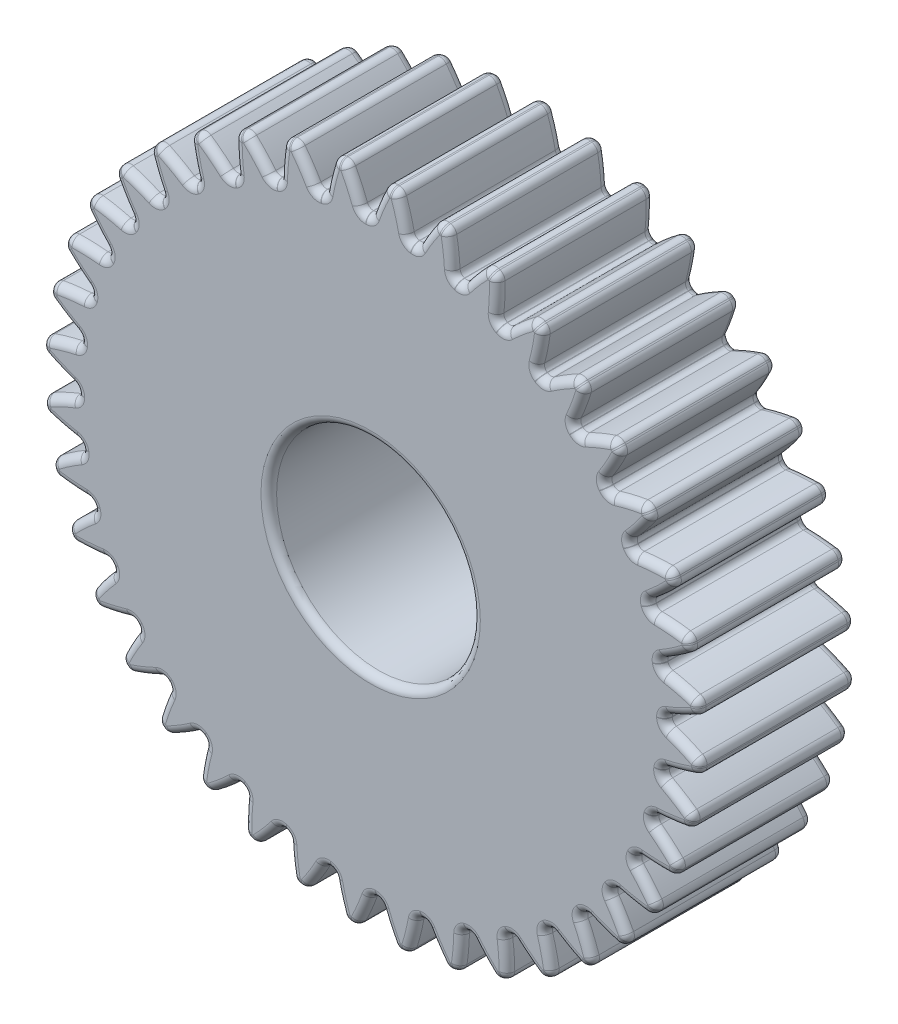
SolidWorks part; units mm, degrees
ref_plane "Front Plane" through (0, 0, 0) normal (1, 0, 0) x (0, 1, 0)
ref_plane "Top Plane" through (0, 0, 0) normal (0, 0, 1) x (0, 1, 0)
ref_plane "Right Plane" through (0, 0, 0) normal (0, 1, 0) x (-1, 0, 0)
sketch "Sketch1" plane through (0, 0, 0) normal (0, 0, 1) x (0, 1, 0)
  line L1 (0, 0) -> (0, 18.7939) construction
  line L2 (0, 0) -> (7.1921, 17.3633) construction
  line L3 (0, 0) -> (13.2893, 13.2893) construction
  line L4 (0, 0) -> (17.3633, 7.1921) construction
  line L5 (0, 0) -> (18.7939, 0) construction
  line L6 (7.1921, 17.3633) -> (0.3736, 20.1876) construction
  line L8 (13.2893, 13.2893) -> (2.8519, 23.7266) construction
  line L9 (17.3633, 7.1921) -> (8.8903, 27.6477) construction
  line L11 (18.7939, 0) -> (18.7939, 29.5213) construction
  line L12 (0, 0) -> (1.2411, 19.9615) construction
  line L14 (2.328, 18.6491) -> (0, 0) construction
  line L17 (0, 18.7939) -> (0, 18.75)
  line L18 (2.328, 18.6491) -> (2.3226, 18.6056)
  line L19 (0.4565, 19.9948) -> (0, 0) construction
  circle A16 centre (0, 0) radius 18.7939 construction
  arc A17 (1.6748, 20.9331) -> (0.9311, 20.9793) centre (0, 0) ccw
  circle A18 centre (0, 0) radius 18.75
  arc A19 (0, 20) -> (2.4774, 19.846) centre (0, 0) ccw construction
  arc A20 (0, 20) -> (2.4774, 19.846) centre (0, 0) cw
  arc A21 (0, 18.7939) -> (8.8903, 27.6477) centre (13.1457, 14.4844) cw construction
  arc A22 (2.328, 18.6491) -> (-5.397, 28.536) centre (-11.2502, 16.0012) ccw construction
  arc A23 (0, 18.7939) -> (0.9311, 20.9793) centre (13.1457, 14.4844) cw
  arc A24 (1.6748, 20.9331) -> (2.328, 18.6491) centre (-11.2502, 16.0012) cw
  circle A25 centre (0, 0) radius 6.5
  point P12 (0, 0)
  dimension "BaseCircle" = 37.5877
  dimension "AddendumCircle" = 42
  dimension "RootCircle" = 37.5
  dimension "PitchCircle" = 40
  dimension "D6" = 13
  dimension "D2" = 29.5213
  dimension "D3" = 22.141
  dimension "D4" = 14.7607
  dimension "D5" = 7.3803
  dimension "D7" = 2.25
  dimension "D1" = 5
sketch "Sketch2" plane through (0, 0, 0) normal (0, 0, 1) x (0, 1, 0)
  line L8 (2.328, 18.6491) -> (2.3226, 18.6056) construction
  line L9 (0, 18.7939) -> (0, 18.75) construction
  line L10 (2.328, 18.6491) -> (2.3226, 18.6056)
  line L11 (0, 18.7939) -> (0, 18.75)
  arc A0 (1.6748, 20.9331) -> (0.9311, 20.9793) centre (0, 0) ccw construction
  arc A1 (1.6748, 20.9331) -> (0.9311, 20.9793) centre (0, 0) ccw
  arc A7 (0.9311, 20.9793) -> (0, 18.7939) centre (13.1457, 14.4844) ccw construction
  arc A8 (0.9311, 20.9793) -> (0, 18.7939) centre (13.1457, 14.4844) ccw
  arc A9 (2.328, 18.6491) -> (1.6748, 20.9331) centre (-11.2502, 16.0012) ccw construction
  arc A10 (2.328, 18.6491) -> (1.6748, 20.9331) centre (-11.2502, 16.0012) ccw
  circle A12 centre (0, 0) radius 18.75 construction
  arc A13 (2.3226, 18.6056) -> (0, 18.75) centre (0, 0) ccw
extrude "Boss-Extrude5" add sketch "Sketch1" along normal blind 10 contours A18 A19 A20
extrude "Boss-Extrude6" add sketch "Sketch2" along normal blind 10
fillet "Fillet3" radius 0.5 4 edges at (-20.9331, 1.6748, 5) (-20.9793, 0.9311, 5) (-18.7939, 0, 5) (-18.6491, 2.328, 5)
fillet "Fillet4" radius 0.4 2 edges at (-18.75, 0, 5) (-18.6056, 2.3226, 5)
pattern_circular "CirPattern5" count 40 over 360 about axis through (0, 0, 0) along (0, 0, 1) of "Boss-Extrude6", "Fillet3", "Fillet4"
fillet "Fillet2" radius 0.5 1 edges at (6.5, 0, 10)
fillet "Fillet5" radius 0.5 641 edges at (-15.8347, 11.9994, 10) (-16.331, 13.0734, 10) (-15.922, 13.5686, 10) (-13.8991, 15.7421, 0) (-13.8991, 15.7421, 10) (-13.7626, 14.3287, 0) (-14.0848, 15.4672, 0) (-13.6033, 15.8923, 0) (-13.7626, 14.3287, 10) (-14.0848, 15.4672, 10) (-13.6033, 15.8923, 10) (-11.2654, 17.7226, 0) (-11.2654, 17.7226, 10) (-11.3517, 16.3052, 0) (-11.4918, 17.4801, 0) (-10.9498, 17.8246, 0) (-11.3517, 16.3052, 10) (-11.4918, 17.4801, 10) (-10.9498, 17.8246, 10) (-8.3543, 19.2667, 0) (-8.3543, 19.2667, 10) (-8.6612, 17.8803, 0) (-8.6158, 19.0626, 0) (-8.0266, 19.3181, 0) (-8.6612, 17.8803, 10) (-8.6158, 19.0626, 10) (-8.0266, 19.3181, 10) (-5.2375, 20.3364, 0) (-5.2375, 20.3364, 10) (-5.7575, 19.0151, 0) (-5.5277, 20.1757, 0) (-4.9057, 20.3359, 0) (-5.7575, 19.0151, 10) (-5.5277, 20.1757, 10) (-4.9057, 20.3359, 10) (-1.9917, 20.9053, 0) (-1.9917, 20.9053, 10) (-2.712, 19.6816, 0) (-2.3035, 20.792, 0) (-1.6641, 20.853, 0) (-2.712, 19.6816, 10) (-2.3035, 20.792, 10) (-1.6641, 20.853, 10) (1.3032, 20.9595, 0) (1.3032, 20.9595, 10) (0.4003, 19.8636, 0) (0.9775, 20.8964, 0) (1.6185, 20.8565, 0) (0.4003, 19.8636, 10) (0.9775, 20.8964, 10) (1.6185, 20.8565, 10) (4.5659, 20.4976, 0) (4.5659, 20.4976, 10) (3.5027, 19.5564, 0) (4.2344, 20.4862, 0) (4.8613, 20.3466, 0) (3.5027, 19.5564, 10) (4.2344, 20.4862, 10) (4.8613, 20.3466, 10) (7.7162, 19.531, 0) (7.7162, 19.531, 10) (6.5189, 18.7677, 0) (7.387, 19.5716, 0) (7.9843, 19.3356, 0) (6.5189, 18.7677, 10) (7.387, 19.5716, 10) (7.9843, 19.3356, 10) (10.6766, 18.0834, 0) (10.6766, 18.0834, 10) (9.3745, 17.5168, 0) (10.3577, 18.1751, 0) (10.9108, 17.8485, 0) (9.3745, 17.5168, 10) (10.3577, 18.1751, 10) (10.9108, 17.8485, 10) (13.374, 16.1906, 0) (13.374, 16.1906, 10) (11.9994, 15.8347, 0) (13.0734, 16.331, 0) (13.5686, 15.922, 0) (11.9994, 15.8347, 10) (13.0734, 16.331, 10) (13.5686, 15.922, 10) (15.7421, 13.8991, 0) (15.7421, 13.8991, 10) (14.3287, 13.7626, 0) (15.4672, 14.0848, 0) (15.8923, 13.6033, 0) (14.3287, 13.7626, 10) (15.4672, 14.0848, 10) (15.8923, 13.6033, 10) (17.7226, 11.2654, 0) (17.7226, 11.2654, 10) (16.3052, 11.3517, 0) (17.4801, 11.4918, 0) (17.8246, 10.9498, 0) (16.3052, 11.3517, 10) (17.4801, 11.4918, 10) (17.8246, 10.9498, 10) (19.2667, 8.3543, 0) (19.2667, 8.3543, 10) (17.8803, 8.6612, 0) (19.0626, 8.6158, 0) (19.3181, 8.0266, 0) (17.8803, 8.6612, 10) (19.0626, 8.6158, 10) (19.3181, 8.0266, 10) (20.3364, 5.2375, 0) (20.3364, 5.2375, 10) (19.0151, 5.7575, 0) (20.1757, 5.5277, 0) (20.3359, 4.9057, 0) (19.0151, 5.7575, 10) (20.1757, 5.5277, 10) (20.3359, 4.9057, 10) (20.9053, 1.9917, 0) (20.9053, 1.9917, 10) (19.6816, 2.712, 0) (20.792, 2.3035, 0) (20.853, 1.6641, 0) (19.6816, 2.712, 10) (20.792, 2.3035, 10) (20.853, 1.6641, 10) (20.9595, -1.3032, 0) (20.9595, -1.3032, 10) (19.8636, -0.4003, 0) (20.8964, -0.9775, 0) (20.8565, -1.6185, 0) (19.8636, -0.4003, 10) (20.8964, -0.9775, 10) (20.8565, -1.6185, 10) (20.4976, -4.5659, 0) (20.4976, -4.5659, 10) (19.5564, -3.5027, 0) (20.4862, -4.2344, 0) (20.3466, -4.8613, 0) (19.5564, -3.5027, 10) (20.4862, -4.2344, 10) (20.3466, -4.8613, 10) (19.531, -7.7162, 0) (19.531, -7.7162, 10) (18.7677, -6.5189, 0) (19.5716, -7.387, 0) (19.3356, -7.9843, 0) (18.7677, -6.5189, 10) (19.5716, -7.387, 10) (19.3356, -7.9843, 10) (18.0834, -10.6766, 0) (18.0834, -10.6766, 10) (17.5168, -9.3745, 0) (18.1751, -10.3577, 0) (17.8485, -10.9108, 0) (17.5168, -9.3745, 10) (18.1751, -10.3577, 10) (-20.9595, 1.3032, 0) (17.8485, -10.9108, 10) (16.1906, -13.374, 0) (16.1906, -13.374, 10) (15.8347, -11.9994, 0) (-20.9595, 1.3032, 10) (16.331, -13.0734, 0) (15.922, -13.5686, 0) (15.8347, -11.9994, 10) (16.331, -13.0734, 10) (15.922, -13.5686, 10) (13.8991, -15.7421, 0) (13.8991, -15.7421, 10) (13.7626, -14.3287, 0) (14.0848, -15.4672, 0) (13.6033, -15.8923, 0) (13.7626, -14.3287, 10) (14.0848, -15.4672, 10) (13.6033, -15.8923, 10) (11.2654, -17.7226, 0) (11.2654, -17.7226, 10) (11.3517, -16.3052, 0) (-19.8636, 0.4003, 0) (11.4918, -17.4801, 0) (10.9498, -17.8246, 0) (11.3517, -16.3052, 10) (11.4918, -17.4801, 10) (10.9498, -17.8246, 10) (8.3543, -19.2667, 0) (8.3543, -19.2667, 10) (8.6612, -17.8803, 0) (8.6158, -19.0626, 0) (8.0266, -19.3181, 0) (8.6612, -17.8803, 10) (8.6158, -19.0626, 10) (8.0266, -19.3181, 10) (5.2375, -20.3364, 0) (5.2375, -20.3364, 10) (5.7575, -19.0151, 0) (5.5277, -20.1757, 0) (4.9057, -20.3359, 0) (5.7575, -19.0151, 10) (5.5277, -20.1757, 10) (4.9057, -20.3359, 10) (-20.8964, 0.9775, 0) (1.9917, -20.9053, 0) (1.9917, -20.9053, 10) (2.712, -19.6816, 0) (2.3035, -20.792, 0) (1.6641, -20.853, 0) (2.712, -19.6816, 10) (2.3035, -20.792, 10) (1.6641, -20.853, 10) (-20.8565, 1.6185, 0) (-1.3032, -20.9595, 0) (-1.3032, -20.9595, 10) (-0.4003, -19.8636, 0) (-0.9775, -20.8964, 0) (-1.6185, -20.8565, 0) (-0.4003, -19.8636, 10) (-0.9775, -20.8964, 10) (-1.6185, -20.8565, 10) (-4.5659, -20.4976, 0) (-4.5659, -20.4976, 10) (-3.5027, -19.5564, 0) (-4.2344, -20.4862, 0) (-4.8613, -20.3466, 0) (-3.5027, -19.5564, 10) (-4.2344, -20.4862, 10) (-4.8613, -20.3466, 10) (-7.7162, -19.531, 0) (-7.7162, -19.531, 10) (-6.5189, -18.7677, 0) (-7.387, -19.5716, 0) (-7.9843, -19.3356, 0) (-6.5189, -18.7677, 10) (-7.387, -19.5716, 10) (-7.9843, -19.3356, 10) (-19.8636, 0.4003, 10) (-10.6766, -18.0834, 0) (-10.6766, -18.0834, 10) (-9.3745, -17.5168, 0) (-10.3577, -18.1751, 0) (-10.9108, -17.8485, 0) (-9.3745, -17.5168, 10) (-10.3577, -18.1751, 10) (-10.9108, -17.8485, 10) (-13.374, -16.1906, 0) (-13.374, -16.1906, 10) (-11.9994, -15.8347, 0) (-13.0734, -16.331, 0) (-13.5686, -15.922, 0) (-11.9994, -15.8347, 10) (-13.0734, -16.331, 10) (-13.5686, -15.922, 10) (-20.8964, 0.9775, 10) (-15.7421, -13.8991, 0) (-15.7421, -13.8991, 10) (-14.3287, -13.7626, 0) (-15.4672, -14.0848, 0) (-15.8923, -13.6033, 0) (-14.3287, -13.7626, 10) (-15.4672, -14.0848, 10) (-15.8923, -13.6033, 10) (-20.8565, 1.6185, 10) (-17.7226, -11.2654, 0) (-17.7226, -11.2654, 10) (-16.3052, -11.3517, 0) (-17.4801, -11.4918, 0) (-17.8246, -10.9498, 0) (-16.3052, -11.3517, 10) (-17.4801, -11.4918, 10) (-17.8246, -10.9498, 10) (-19.2667, -8.3543, 0) (-19.2667, -8.3543, 10) (-17.8803, -8.6612, 0) (-19.0626, -8.6158, 0) (-19.3181, -8.0266, 0) (-17.8803, -8.6612, 10) (-19.0626, -8.6158, 10) (-19.3181, -8.0266, 10) (-20.3364, -5.2375, 0) (-20.3364, -5.2375, 10) (-19.0151, -5.7575, 0) (-20.1757, -5.5277, 0) (-20.3359, -4.9057, 0) (-19.0151, -5.7575, 10) (-20.1757, -5.5277, 10) (-20.3359, -4.9057, 10) (-20.9053, -1.9917, 0) (-20.9053, -1.9917, 10) (-19.6816, -2.712, 0) (-20.792, -2.3035, 0) (-20.853, -1.6641, 0) (-19.6816, -2.712, 10) (-20.792, -2.3035, 10) (-20.853, -1.6641, 10) (-18.5649, 2.6282, 0) (-18.5649, 2.6282, 10) (-19.1941, 5.1291, 0) (-19.1941, 5.1291, 10) (-18.6025, 2.8772, 0) (6.5, 0, 0) (-18.6025, 2.8772, 10) (-18.0649, 5.2906, 0) (-18.0649, 5.2906, 10) (-17.9252, 5.5001, 0) (-17.9252, 5.5001, 10) (-18.1554, 8.0686, 0) (-18.1554, 8.0686, 10) (-17.9234, 5.7518, 0) (-17.9234, 5.7518, 10) (-17.0148, 8.0514, 0) (-17.0148, 8.0514, 10) (-16.8441, 8.2365, 0) (-16.8441, 8.2365, 10) (-16.6697, 10.8094, 0) (-16.6697, 10.8094, 10) (-16.8029, 8.4848, 0) (-16.8029, 8.4848, 10) (-15.5458, 10.614, 0) (-15.5458, 10.614, 10) (-15.3482, 10.7701, 0) (-15.3482, 10.7701, 10) (-14.7735, 13.284, 0) (-14.7735, 13.284, 10) (-15.2687, 11.0089, 0) (-15.2687, 11.0089, 10) (-13.694, 12.9153, 0) (-13.694, 12.9153, 10) (-13.4745, 13.0384, 0) (-13.4745, 13.0384, 10) (-12.5135, 15.4315, 0) (-12.5135, 15.4315, 10) (-13.3586, 13.262, 0) (-13.3586, 13.262, 10) (-11.5051, 14.8985, 0) (-11.5051, 14.8985, 10) (-11.2689, 14.9858, 0) (-11.2689, 14.9858, 10) (-9.9455, 17.1991, 0) (-9.9455, 17.1991, 10) (-11.1195, 15.1884, 0) (-11.1195, 15.1884, 10) (-9.0328, 16.5148, 0) (-9.0328, 16.5148, 10) (-8.7859, 16.5641, 0) (-8.7859, 16.5641, 10) (-7.1325, 18.5432, 0) (-7.1325, 18.5432, 10) (-8.6066, 16.7409, 0) (-8.6066, 16.7409, 10) (-6.3381, 17.7245, 0) (-6.3381, 17.7245, 10) (-6.0865, 17.7346, 0) (-6.0865, 17.7346, 10) (-4.1439, 19.4306, 0) (-4.1439, 19.4306, 10) (-5.8818, 17.8812, 0) (-5.8818, 17.8812, 10) (-3.4873, 18.4978, 0) (-3.4873, 18.4978, 10) (-3.2373, 18.4684, 0) (-3.2373, 18.4684, 10) (-1.0532, 19.8397, 0) (-1.0532, 19.8397, 10) (-3.0121, 18.5811, 0) (-3.0121, 18.5811, 10) (-0.5507, 18.8156, 0) (-0.5507, 18.8156, 10) (-0.3083, 18.7475, 0) (-0.3083, 18.7475, 10) (2.0633, 19.7602, 0) (2.0633, 19.7602, 10) (-0.0683, 18.8236, 0) (-0.0683, 18.8236, 10) (2.3995, 18.6701, 0) (2.3995, 18.6701, 10) (2.6282, 18.5649, 0) (2.6282, 18.5649, 10) (5.1291, 19.1941, 0) (5.1291, 19.1941, 10) (2.8772, 18.6025, 0) (2.8772, 18.6025, 10) (5.2906, 18.0649, 0) (5.2906, 18.0649, 10) (5.5001, 17.9252, 0) (5.5001, 17.9252, 10) (8.0686, 18.1554, 0) (8.0686, 18.1554, 10) (5.7518, 17.9234, 0) (5.7518, 17.9234, 10) (8.0514, 17.0148, 0) (8.0514, 17.0148, 10) (8.2365, 16.8441, 0) (8.2365, 16.8441, 10) (10.8094, 16.6697, 0) (10.8094, 16.6697, 10) (8.4848, 16.8029, 0) (8.4848, 16.8029, 10) (10.614, 15.5458, 0) (10.614, 15.5458, 10) (10.7701, 15.3482, 0) (10.7701, 15.3482, 10) (13.284, 14.7735, 0) (13.284, 14.7735, 10) (11.0089, 15.2687, 0) (11.0089, 15.2687, 10) (12.9153, 13.694, 0) (12.9153, 13.694, 10) (13.0384, 13.4745, 0) (13.0384, 13.4745, 10) (15.4315, 12.5135, 0) (15.4315, 12.5135, 10) (13.262, 13.3586, 0) (13.262, 13.3586, 10) (14.8985, 11.5051, 0) (14.8985, 11.5051, 10) (14.9858, 11.2689, 0) (14.9858, 11.2689, 10) (17.1991, 9.9455, 0) (17.1991, 9.9455, 10) (15.1884, 11.1195, 0) (15.1884, 11.1195, 10) (16.5148, 9.0328, 0) (16.5148, 9.0328, 10) (16.5641, 8.7859, 0) (16.5641, 8.7859, 10) (18.5432, 7.1325, 0) (18.5432, 7.1325, 10) (16.7409, 8.6066, 0) (16.7409, 8.6066, 10) (17.7245, 6.3381, 0) (17.7245, 6.3381, 10) (17.7346, 6.0865, 0) (17.7346, 6.0865, 10) (19.4306, 4.1439, 0) (19.4306, 4.1439, 10) (17.8812, 5.8818, 0) (17.8812, 5.8818, 10) (18.4978, 3.4873, 0) (18.4978, 3.4873, 10) (18.4684, 3.2373, 0) (18.4684, 3.2373, 10) (19.8397, 1.0532, 0) (19.8397, 1.0532, 10) (18.5811, 3.0121, 0) (18.5811, 3.0121, 10) (18.8156, 0.5507, 0) (18.8156, 0.5507, 10) (18.7475, 0.3083, 0) (18.7475, 0.3083, 10) (19.7602, -2.0633, 0) (19.7602, -2.0633, 10) (18.8236, 0.0683, 0) (18.8236, 0.0683, 10) (18.6701, -2.3995, 0) (18.6701, -2.3995, 10) (18.5649, -2.6282, 0) (18.5649, -2.6282, 10) (19.1941, -5.1291, 0) (19.1941, -5.1291, 10) (18.6025, -2.8772, 0) (18.6025, -2.8772, 10) (18.0649, -5.2906, 0) (18.0649, -5.2906, 10) (17.9252, -5.5001, 0) (17.9252, -5.5001, 10) (18.1554, -8.0686, 0) (18.1554, -8.0686, 10) (17.9234, -5.7518, 0) (17.9234, -5.7518, 10) (17.0148, -8.0514, 0) (17.0148, -8.0514, 10) (16.8441, -8.2365, 0) (16.8441, -8.2365, 10) (16.6697, -10.8094, 0) (16.6697, -10.8094, 10) (16.8029, -8.4848, 0) (16.8029, -8.4848, 10) (15.5458, -10.614, 0) (15.5458, -10.614, 10) (15.3482, -10.7701, 0) (15.3482, -10.7701, 10) (14.7735, -13.284, 0) (14.7735, -13.284, 10) (15.2687, -11.0089, 0) (15.2687, -11.0089, 10) (13.694, -12.9153, 0) (13.694, -12.9153, 10) (-18.7475, -0.3083, 0) (13.4745, -13.0384, 0) (13.4745, -13.0384, 10) (12.5135, -15.4315, 0) (12.5135, -15.4315, 10) (13.3586, -13.262, 0) (13.3586, -13.262, 10) (11.5051, -14.8985, 0) (11.5051, -14.8985, 10) (-18.7475, -0.3083, 10) (11.2689, -14.9858, 0) (11.2689, -14.9858, 10) (9.9455, -17.1991, 0) (9.9455, -17.1991, 10) (11.1195, -15.1884, 0) (11.1195, -15.1884, 10) (9.0328, -16.5148, 0) (9.0328, -16.5148, 10) (8.7859, -16.5641, 0) (8.7859, -16.5641, 10) (7.1325, -18.5432, 0) (7.1325, -18.5432, 10) (8.6066, -16.7409, 0) (8.6066, -16.7409, 10) (6.3381, -17.7245, 0) (6.3381, -17.7245, 10) (6.0865, -17.7346, 0) (6.0865, -17.7346, 10) (4.1439, -19.4306, 0) (4.1439, -19.4306, 10) (5.8818, -17.8812, 0) (5.8818, -17.8812, 10) (3.4873, -18.4978, 0) (3.4873, -18.4978, 10) (3.2373, -18.4684, 0) (3.2373, -18.4684, 10) (1.0532, -19.8397, 0) (1.0532, -19.8397, 10) (3.0121, -18.5811, 0) (3.0121, -18.5811, 10) (0.5507, -18.8156, 0) (0.5507, -18.8156, 10) (0.3083, -18.7475, 0) (0.3083, -18.7475, 10) (-2.0633, -19.7602, 0) (-2.0633, -19.7602, 10) (0.0683, -18.8236, 0) (0.0683, -18.8236, 10) (-2.3995, -18.6701, 0) (-2.3995, -18.6701, 10) (-2.6282, -18.5649, 0) (-2.6282, -18.5649, 10) (-5.1291, -19.1941, 0) (-5.1291, -19.1941, 10) (-2.8772, -18.6025, 0) (-2.8772, -18.6025, 10) (-5.2906, -18.0649, 0) (-5.2906, -18.0649, 10) (-5.5001, -17.9252, 0) (-5.5001, -17.9252, 10) (-8.0686, -18.1554, 0) (-8.0686, -18.1554, 10) (-5.7518, -17.9234, 0) (-5.7518, -17.9234, 10) (-19.7602, 2.0633, 0) (-8.0514, -17.0148, 0) (-8.0514, -17.0148, 10) (-19.7602, 2.0633, 10) (-8.2365, -16.8441, 0) (-8.2365, -16.8441, 10) (-10.8094, -16.6697, 0) (-10.8094, -16.6697, 10) (-8.4848, -16.8029, 0) (-8.4848, -16.8029, 10) (-10.614, -15.5458, 0) (-10.614, -15.5458, 10) (-10.7701, -15.3482, 0) (-10.7701, -15.3482, 10) (-13.284, -14.7735, 0) (-13.284, -14.7735, 10) (-11.0089, -15.2687, 0) (-11.0089, -15.2687, 10) (-12.9153, -13.694, 0) (-12.9153, -13.694, 10) (-18.8236, -0.0683, 0) (-13.0384, -13.4745, 0) (-13.0384, -13.4745, 10) (-15.4315, -12.5135, 0) (-15.4315, -12.5135, 10) (-13.262, -13.3586, 0) (-13.262, -13.3586, 10) (-14.8985, -11.5051, 0) (-14.8985, -11.5051, 10) (-18.8236, -0.0683, 10) (-14.9858, -11.2689, 0) (-14.9858, -11.2689, 10) (-17.1991, -9.9455, 0) (-17.1991, -9.9455, 10) (-15.1884, -11.1195, 0) (-15.1884, -11.1195, 10) (-16.5148, -9.0328, 0) (-16.5148, -9.0328, 10) (-16.5641, -8.7859, 0) (-16.5641, -8.7859, 10) (-18.5432, -7.1325, 0) (-18.5432, -7.1325, 10) (-16.7409, -8.6066, 0) (-16.7409, -8.6066, 10) (-18.6701, 2.3995, 0) (-17.7245, -6.3381, 0) (-17.7245, -6.3381, 10) (-17.7346, -6.0865, 0) (-17.7346, -6.0865, 10) (-19.4306, -4.1439, 0) (-19.4306, -4.1439, 10) (-17.8812, -5.8818, 0) (-17.8812, -5.8818, 10) (-18.4978, -3.4873, 0) (-18.4978, -3.4873, 10) (-18.6701, 2.3995, 10) (-18.4684, -3.2373, 0) (-18.4684, -3.2373, 10) (-19.8397, -1.0532, 0) (-19.8397, -1.0532, 10) (-18.5811, -3.0121, 0) (-18.5811, -3.0121, 10) (-18.8156, -0.5507, 0) (-18.8156, -0.5507, 10) (-20.4976, 4.5659, 0) (-20.4976, 4.5659, 10) (-19.5564, 3.5027, 0) (-20.4862, 4.2344, 0) (-20.3466, 4.8613, 0) (-19.5564, 3.5027, 10) (-20.4862, 4.2344, 10) (-20.3466, 4.8613, 10) (-19.531, 7.7162, 0) (-19.531, 7.7162, 10) (-18.7677, 6.5189, 0) (-19.5716, 7.387, 0) (-19.3356, 7.9843, 0) (-18.7677, 6.5189, 10) (-19.5716, 7.387, 10) (-19.3356, 7.9843, 10) (-18.0834, 10.6766, 0) (-18.0834, 10.6766, 10) (-17.5168, 9.3745, 0) (-18.1751, 10.3577, 0) (-17.8485, 10.9108, 0) (-17.5168, 9.3745, 10) (-18.1751, 10.3577, 10) (-17.8485, 10.9108, 10) (-16.1906, 13.374, 0) (-16.1906, 13.374, 10) (-15.8347, 11.9994, 0) (-16.331, 13.0734, 0) (-15.922, 13.5686, 0)
equation "\"PlanetTeeth\" = 40"
equation "\"Module\" = 1"
equation "\"PressureAngle\" = 20deg"
equation "\"PitchDiameter\"= \"PlanetTeeth\" * \"Module\""
equation "\"OutsideDiameter\"= (\"PlanetTeeth\" + 2) * \"Module\""
equation "\"WholeDepthDia\"= (\"PlanetTeeth\" - 2.5) * \"Module\""
equation "\"BaseCircleDia\"= \"PitchDiameter\" * cos(\"PressureAngle\")"
equation "\"Addendum\"= 1 * \"Module\""
equation "\"Dedendum\"= 1.25 * \"Module\""
equation "\"WholeDepth\"= 2.25 * \"Module\""
equation "\"CircularPitch\"= 360 / \"PlanetTeeth\""
equation "\"FilletRadius\"= \"Module\" / 2"
equation "\"PitchArcLength\"= ( \"CircularPitch\" / 180 * 3.14 * \"BaseCircleDia\" / 2 )"
equation "\"BaseCircle@Sketch1\" = \"BaseCircleDia\""
equation "\"AddendumCircle@Sketch1\"= \"PitchCircle@Sketch1\" + \"Addendum\" * 2"
equation "\"RootCircle@Sketch1\"=\"PitchCircle@Sketch1\" - \"Dedendum\" * 2"
equation "\"PitchCircle@Sketch1\" = \"Module\" * \"PlanetTeeth\""
equation "\"InvoluteArrayMaxLength\"= \"BaseCircleDia\" * pi / 4"
equation "\"D2@Sketch1\"=\"InvoluteArrayMaxLength\""
equation "\"D3@Sketch1\"=\"InvoluteArrayMaxLength\"*3/4"
equation "\"D4@Sketch1\"=\"InvoluteArrayMaxLength\"*2/4"
equation "\"D5@Sketch1\"=\"InvoluteArrayMaxLength\"*1/4"
equation "\"GearWidth\"=10"
equation "\"BearingDiameter\" = 13"
equation "\"D6@Sketch1\" = IIF ( \"PitchCircle@Sketch1\" > \"BearingDiameter\" , \"BearingDiameter\" , \"PitchCircle@Sketch1\" - 3 )"
equation "\"D1@CirPattern5\"=\"PlanetTeeth\""
equation "\"D1@Boss-Extrude6\"=\"GearWidth\""
equation "\"D7@Sketch1\"=\"CircularPitch\"/4"
equation "\"D1@Fillet3\"=\"FilletRadius\""
